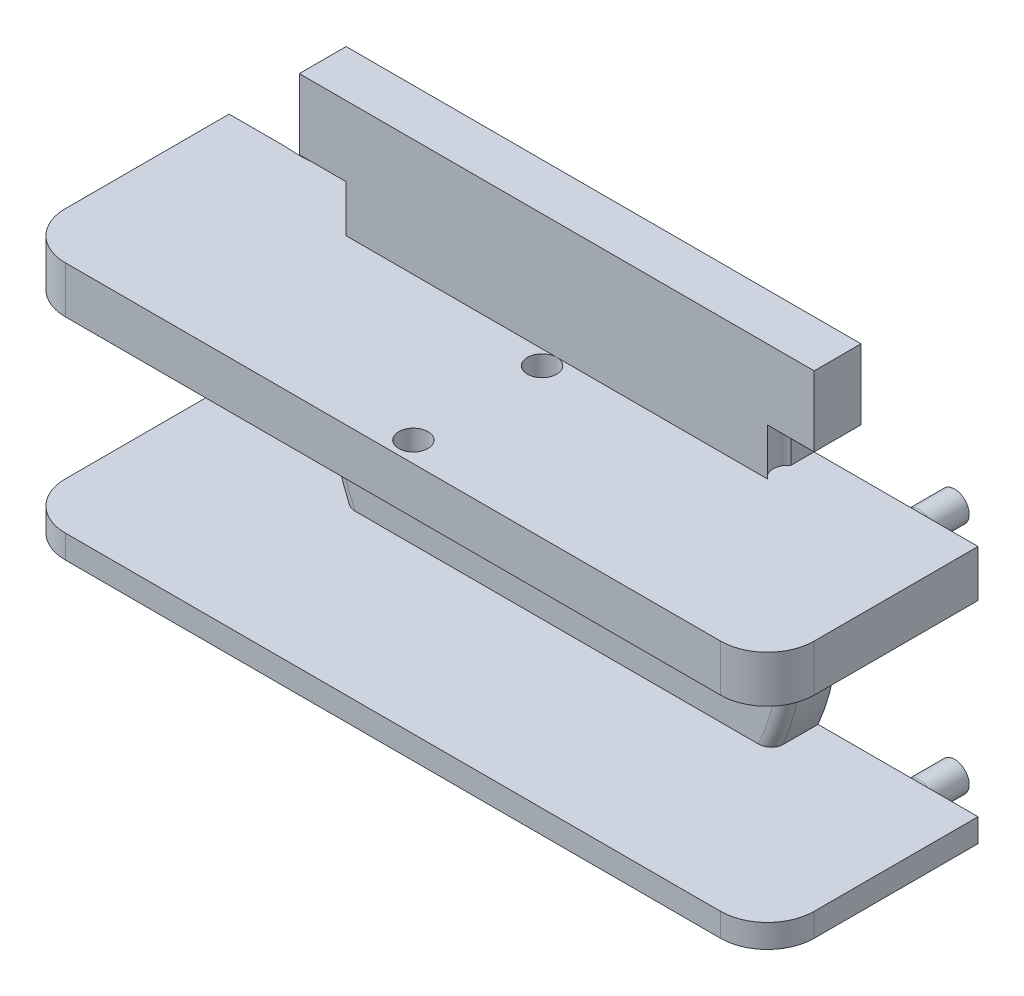
SolidWorks part; units mm, degrees
material "UNOBTANIUM"
ref_plane "Top Plane" through (0, 0, 0) normal (0, 0, 1) x (1, 0, 0)
ref_plane "Right Plane" through (0, 0, 0) normal (0, 1, 0) x (1, 0, 0)
ref_plane "Front Plane" through (0, 0, 0) normal (1, 0, 0) x (0, 0, -1)
ref_axis "x-axis" through (-17.6, 0, 0) along (1, 0, 0)
ref_axis "y-axis" through (0, -9.7375, 0) along (0, 1, 0)
ref_axis "z-axis" through (0, 0, 8.775) along (0, 0, -1)
sketch "Sketch1" plane through (0, 0, 0) normal (0, 0, 1) x (1, 0, 0)
  line L0 (-11, 6) -> (-11, 11)
  line L1 (-11, -6) -> (11, -6)
  line L2 (-11, -6) -> (-11, 6)
  line L3 (-11, 6) -> (11, 6) construction
  line L4 (11, -6) -> (11, 6)
  line L5 (-11, -6) -> (11, 6) construction
  line L6 (-11, 6) -> (11, -6) construction
  line L7 (-11, 11) -> (11, 11)
  line L8 (11, 11) -> (11, 6)
  circle A0 centre (0, 0) radius 9.25 construction
  point P0 (0, 0)
  dimension "D1" = 18.5
  dimension "D2" = 22
  dimension "D3" = 12
  dimension "D4" = 5
extrude "Boss-Extrude1" add sketch "Sketch1" along normal blind 2
sketch "Sketch2" plane through (0, 0, 2) normal (0, 0, -1) x (-1, 0, 0)
  circle A0 centre (0, 0) radius 1.575
  dimension "D1" = 3.15
extrude "Boss-Extrude2" add sketch "Sketch2" along normal blind 4 separate body
sketch "Sketch3" plane through (0, 0, 0) normal (0, 0, -1) x (-1, 0, 0)
  line L0 (11, -6) -> (-11, 6) construction
  circle A0 centre (0, 0) radius 1.8
  dimension "D1" = 3.6
extrude "Boss-Extrude3" add sketch "Sketch3" along normal blind 0.4
sketch "Sketch4" plane through (0, 0, 0) normal (0, 0, -1) x (-1, 0, 0)
  line L0 (11, -6) -> (-11, -6) construction
  line L1 (11, 11) -> (9, 11)
  line L2 (11, 11) -> (11, -6)
  line L3 (11, -6) -> (9, -6)
  line L4 (9, 11) -> (9, -6)
  line L5 (0, -6) -> (0, 11) construction
  line L7 (-9, 11) -> (-9, -6)
  line L8 (-11, -6) -> (-9, -6)
  line L9 (-11, 11) -> (-11, -6)
  line L10 (-11, 11) -> (-9, 11)
  line L11 (11, 11) -> (-11, 11) construction
  dimension "D1" = 2
extrude "Boss-Extrude4" add sketch "Sketch4" along normal blind 0.001
sketch "Sketch5" plane through (0, 0, 0) normal (0, 0, -1) x (-1, 0, 0)
  line L0 (-9, -6) -> (-9, 11) construction
  line L1 (9, 11) -> (-9, 11)
  line L2 (9, 11) -> (9, 9)
  line L3 (9, 9) -> (-9, 9)
  line L4 (-9, 11) -> (-9, 9)
  dimension "D1" = 2
extrude "Boss-Extrude5" add sketch "Sketch5" along normal up to surface (0.001 mm away) up to face at (-10, 2.5, -0.001)
sketch "Sketch6" plane through (11, 0, 0) normal (1, 0, 0) x (0, 0, -1)
  line L0 (-2, -6) -> (-2, 11) construction
  line L1 (0.001, -6) -> (-2, -6)
  line L2 (0.001, -6) -> (0.001, -4)
  line L3 (0.001, -4) -> (-2, -4)
  line L4 (-2, -6) -> (-2, -4)
  line L6 (0.001, 11) -> (0.001, -6) construction
  line L7 (-2, 6) -> (0.001, 6)
  line L8 (-2, 6) -> (-2, 4)
  line L9 (-2, 4) -> (0.001, 4)
  line L10 (0.001, 6) -> (0.001, 4)
  dimension "D1" = 2
extrude "Boss-Extrude6" add sketch "Sketch6" along normal blind 5
mirror "Mirror1" about plane through (0, 0, 0) normal (1, 0, 0) of "Boss-Extrude6"
sketch "Sketch7" plane through (0, 0, -0.001) normal (0, 0, -1) x (-1, 0, 0)
  line L0 (-9, -6) -> (-9, 9) construction
  line L1 (-9, 0) -> (-9, 9)
  line L2 (-9, 9) -> (0, 9)
  line L3 (-9, 0) -> (-9, -6)
  line L4 (-9, -6) -> (-6.7082, -6)
  line L5 (11, -6) -> (-11, -6) construction
  arc A0 (0, 9) -> (-6.7082, -6) centre (0, 0) ccw
  line M18 (-9, -6) -> (-9, 9)
  line M19 (-9, 9) -> (9, 9)
extrude "Boss-Extrude7" add sketch "Sketch7" against normal up to surface (0.001 mm away) contours A0 L4 M18 | A0 M19 M18 region at (8.3306, -4.5409, -0.001) region at (6.9897, 6.9897, -0.001) up to face at (1.8, 0, 0)
sketch "Sketch8" plane through (0, 0, -0.001) normal (0, 0, -1) x (-1, 0, 0)
  line L0 (-11, 4) -> (-9.1652, 4)
  line L1 (-11, 4) -> (-11, -4)
  line L2 (-11, -4) -> (-9.1652, -4)
  arc A1 (-9.1652, 4) -> (-9.1652, -4) centre (0, 0) ccw
  dimension "D1" = 10
extrude "Cut-Extrude1" cut sketch "Sketch8" against normal through all
sketch "Sketch9" plane through (0, 0, -0.001) normal (0, 0, -1) x (-1, 0, 0)
  line L0 (-16, -4) -> (-9.1652, -4) construction
  line L1 (-8.0623, 4) -> (-11, 4)
  line L2 (-8.0623, 4) -> (-8.0623, -4)
  line L3 (-8.0623, -4) -> (-11, -4)
  line L4 (-11, 4) -> (-11, -4)
  line L5 (-11, -6) -> (-11, 6) construction
  arc A0 (0, 9) -> (-6.7082, -6) centre (0, 0) ccw construction
  arc A1 (0, 9) -> (-6.7082, -6) centre (0, 0) ccw construction
extrude "Cut-Extrude2" cut sketch "Sketch9" against normal up to surface (0.001 mm away) up to face at (1.8, 0, 0)
mirror "Mirror2" about plane through (0, 0, 0) normal (1, 0, 0) of "Cut-Extrude2", "Boss-Extrude7", "Cut-Extrude1"
sketch "Sketch21" plane through (0, 0, -0.001) normal (0, 0, -1) x (-1, 0, 0)
  circle A0 centre (0, 0) radius 9.75
  circle A1 centre (0, 0) radius 9 construction
  circle A2 centre (0, 0) radius 1.8 construction
  circle A3 centre (0, 0) radius 1.8
  dimension "D1" = 0.75
extrude "Cut-Extrude11" cut sketch "Sketch21" against normal up to surface (0.001 mm away) up to face at (0, -0.7091, 0)
sketch "Sketch10" plane through (0, 0, 2) normal (0, 0, 1) x (1, 0, 0)
  line L0 (-16, -4) -> (-16, -6) construction
  line L1 (16, -6) -> (-16, -6)
  line L2 (16, -6) -> (16, -4)
  line L3 (16, -4) -> (-16, -4)
  line L4 (-16, -6) -> (-16, -4)
  line L5 (-16, -4) -> (-9.1652, -4) construction
  line L7 (-16, 6) -> (16, 6)
  line L8 (-16, 6) -> (-16, 4)
  line L9 (-16, 4) -> (16, 4)
  line L10 (16, 6) -> (16, 4)
extrude "Boss-Extrude8" add sketch "Sketch10" along normal blind 7
fillet "Fillet1" radius 0.5 2 edges at (10, 0, 2) (-10, 0, 2)
sketch "Sketch11" plane through (0, 0, -0.001) normal (0, 0, -1) x (-1, 0, 0)
  line L0 (-16, -5) -> (-13, -5) construction
  line L1 (-16, -6) -> (-16, -4) construction
  circle A0 centre (-13, -5) radius 0.625
  dimension "D1" = 1.25
  dimension "D2" = 3
extrude "Boss-Extrude9" add sketch "Sketch11" along normal blind 2
sketch "Sketch14" plane through (0, 0, -0.001) normal (0, 0, -1) x (-1, 0, 0)
  line L1 (11, 6) -> (9, 6)
  line L2 (11, 6) -> (11, 8)
  line L3 (11, 8) -> (9, 8)
  line L4 (9, 6) -> (9, 8)
  line L5 (-11, 6) -> (-9, 6)
  line L6 (-11, 6) -> (-11, 8)
  line L7 (-11, 8) -> (-9, 8)
  line L8 (-9, 6) -> (-9, 8)
  dimension "D1" = 18
  dimension "D2" = 2
extrude "Cut-Extrude5" cut sketch "Sketch14" against normal through all
sketch "Sketch12" plane through (0, 0, -0.001) normal (0, 0, -1) x (-1, 0, 0)
  line L0 (-16, -5) -> (-13, -5) construction
  line L1 (-16, -6) -> (-16, -4) construction
  line L3 (16, -5) -> (13, -5) construction
  line L4 (16, -6) -> (16, -4) construction
  circle A0 centre (13, -5) radius 0.675
  circle A1 centre (-13, -5) radius 0.625 construction
  circle A2 centre (-13, -5) radius 0.625 construction
  dimension "D1" = 1.35
  dimension "D2" = 1.25
extrude "Cut-Extrude3" cut sketch "Sketch12" against normal blind 2.5
sketch "Sketch16" plane through (0, 6, 0) normal (0, 1, 0) x (1, 0, 0)
  line L0 (-9, -2) -> (-9, 0.001) construction
  line L1 (-9, -1) -> (-9, -2)
  arc A1 (-9, -1) -> (-9, -2) centre (-9.375, -1.5) cw
  dimension "D1" = 0.25
  dimension "D2" = 1
extrude "Cut-Extrude6" cut sketch "Sketch16" along normal blind 2
mirror "Mirror3" about plane through (0, 0, 0) normal (0, 1, 0) of "Boss-Extrude9", "Cut-Extrude3"
mirror "Mirror4" about plane through (0, 0, 0) normal (1, 0, 0) of "Cut-Extrude6"
fillet "Fillet2" radius 0.5 2 edges at (12.375, 5, -0.001) (13.625, -5, -0.001)
fillet "Fillet3" radius 0.5 2 edges at (-13.675, 5, -0.001) (-13.675, -5, -0.001)
fillet "Fillet4" radius 2 4 edges at (16, -5, 9) (16, 5, 9) (-16, -5, 9) (-16, 5, 9)
sketch "Sketch17" plane through (0, -6, 0) normal (0, -1, 0) x (1, 0, 0)
  line L0 (-16, 7) -> (-16, -0.001) construction
  line L1 (-14, 9) -> (14, 9) construction
  line L2 (16, 7) -> (16, -0.001) construction
  line L3 (-16, 7) -> (-16, -0.001)
  line L4 (-14, 9) -> (14, 9)
  line L5 (16, 7) -> (16, -0.001)
  line L6 (14.5, 7) -> (14.5, -0.001)
  line L8 (-14, 7.5) -> (14, 7.5)
  line L9 (-14.5, 7) -> (-14.5, -0.001)
  line L10 (14.5, -0.001) -> (16, -0.001)
  line L11 (-14.5, -0.001) -> (-16, -0.001)
  arc A0 (-14, 9) -> (-16, 7) centre (-14, 7) ccw construction
  arc A1 (16, 7) -> (14, 9) centre (14, 7) ccw construction
  arc A2 (-14, 9) -> (-16, 7) centre (-14, 7) ccw
  arc A3 (16, 7) -> (14, 9) centre (14, 7) ccw
  arc A4 (14.5, 7) -> (14, 7.5) centre (14, 7) ccw
  arc A5 (-14, 7.5) -> (-14.5, 7) centre (-14, 7) ccw
  dimension "D1" = 1.5
extrude "Cut-Extrude7" cut sketch "Sketch17" against normal blind 1 and the other way through all
sketch "Sketch19" plane through (0, 6, 0) normal (0, 1, 0) x (1, 0, 0)
  line L0 (9, -2) -> (-9, -2) construction
  line L1 (0, -2.625) -> (0, -2) construction
  line L2 (9, -2) -> (-9, -2) construction
  circle A0 centre (0, -2.625) radius 0.625
  circle A1 centre (0, -8.125) radius 0.625
  point P4 (0, -2)
  dimension "D1" = 1.25
  dimension "D2" = 5.5
extrude "Cut-Extrude9" cut sketch "Sketch19" against normal up to surface (2 mm away) up to face at (0.0154, 4, 1.9997)
sketch "Sketch20" plane through (0, 0, -0.001) normal (0, 0, -1) x (-1, 0, 0)
  line L0 (-9, 8) -> (-11, 8) construction
  line L1 (-11, 11) -> (-9, 11)
  line L2 (-11, 11) -> (-11, 8)
  line L3 (-11, 8) -> (-9, 8)
  line L4 (-9, 11) -> (-9, 8)
  line L5 (11, 11) -> (-11, 11) construction
  line L6 (11, 8) -> (9, 8)
  line L7 (11, 8) -> (11, 11)
  line L8 (11, 11) -> (9, 11)
  line L9 (9, 8) -> (9, 11)
  dimension "D1" = 2
combine bodies "Combine2" operation type subtract main body 122 bodies to subtract 102
equation "\"D1@Sketch12\"=\"D2@Sketch12\"+.1"
